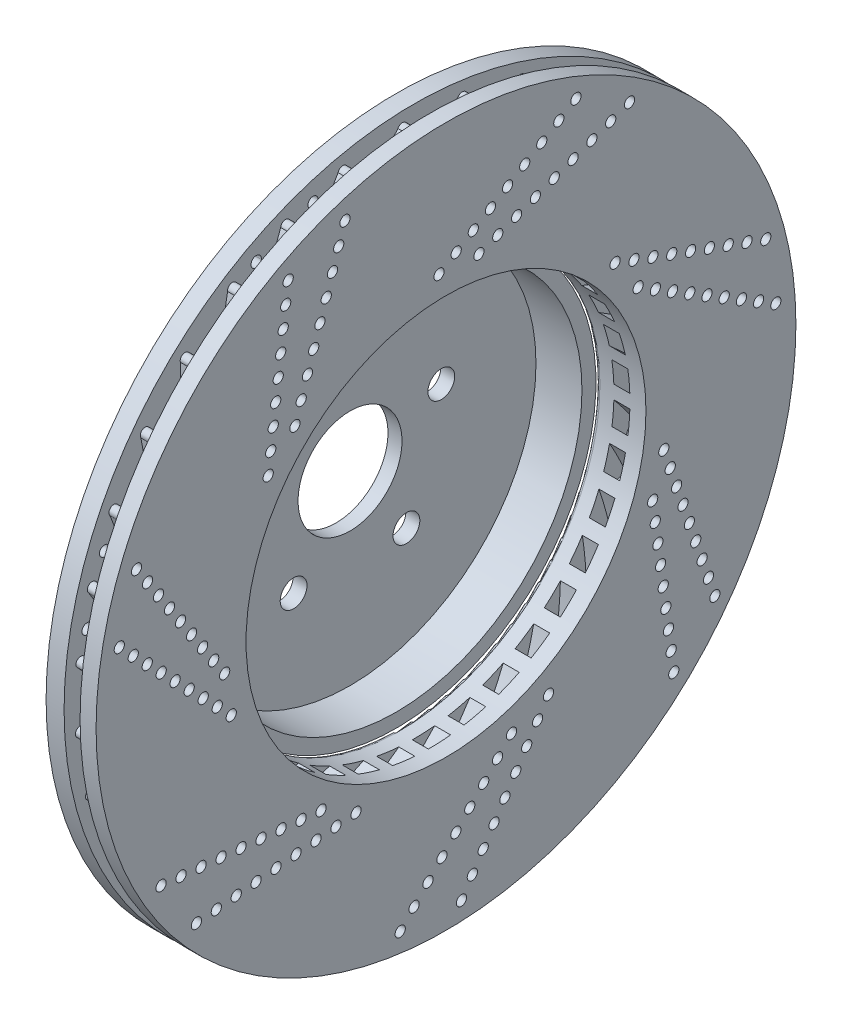
SolidWorks part; units mm, degrees
other "Markup1"
sketch "Sketch13"
ref_plane "Front Plane" through (0, 0, 0) normal (0, 0, 1) x (1, 0, 0)
ref_plane "Top Plane" through (0, 0, 0) normal (0, 1, 0) x (1, 0, 0)
ref_plane "Right Plane" through (0, 0, 0) normal (1, 0, 0) x (0, 0, -1)
sketch "Sketch2" plane through (0, 0, 0) normal (1, 0, 0) x (0, 0, -1)
  circle A0 centre (0, 0) radius 87.5
  dimension "D1" = 175
extrude "Boss-Extrude1" add sketch "Sketch2" along normal blind 4.5
sketch "Sketch3" plane through (4.5, 0, 0) normal (1, 0, 0) x (0, 0, -1)
  circle A0 centre (0, 0) radius 50
  dimension "D1" = 100
extrude "Cut-Extrude1" cut sketch "Sketch3" against normal through all
sketch "Sketch4" plane through (4.5, 0, 0) normal (1, 0, 0) x (0, 0, -1)
  line L0 (0, 0) -> (0, -87.5) construction
  line L1 (-22.5, -50.7346) -> (-71.6537, -55.6408) construction
  line L2 (-31.239, -45.8735) -> (-82.8176, -41.0887) construction
  circle A0 centre (0, 0) radius 55.5 construction
  circle A1 centre (0, 0) radius 87.5 construction
  circle A2 centre (-22.5, -50.7346) radius 1.28
  circle A3 centre (-31.239, -45.8735) radius 1.28
  circle A4 centre (-27.5, -51.2337) radius 1.28
  circle A5 centre (-32.5, -51.7327) radius 1.28
  circle A6 centre (-37.5, -52.2318) radius 1.28
  circle A7 centre (-42.5, -52.7309) radius 1.28
  circle A8 centre (-47.5, -53.2299) radius 1.28
  circle A9 centre (-52.5, -53.729) radius 1.28
  circle A10 centre (-57.5, -54.2281) radius 1.28
  circle A11 centre (-62.5, -54.7271) radius 1.28
  circle A12 centre (-36.239, -45.4097) radius 1.28
  circle A13 centre (-41.239, -44.9458) radius 1.28
  circle A14 centre (-46.239, -44.482) radius 1.28
  circle A15 centre (-51.2176, -44.0201) radius 1.28
  circle A16 centre (-46.239, -44.482) radius 1.28
  circle A17 centre (-56.2176, -43.5563) radius 1.28
  circle A18 centre (-61.2176, -43.0925) radius 1.28
  circle A19 centre (-66.2176, -42.6286) radius 1.28
  dimension "D1" = 111
  dimension "D2" = 2.56
  dimension "D3" = 10
  dimension "D7" = 5
  dimension "D15" = 5
  dimension "D16" = 5
  dimension "D17" = 5
  dimension "D18" = 5
  dimension "D19" = 5
  dimension "D20" = 5
  dimension "D21" = 5
  dimension "D4" = 22.5
  dimension "D5" = 84.3
  dimension "D6" = 95.3
  dimension "D8" = 5
  dimension "D9" = 5
  dimension "D10" = 5
  dimension "D11" = 5
  dimension "D12" = 5
  dimension "D13" = 5
  dimension "D14" = 5
  dimension "D22" = 5
extrude "Cut-Extrude6" cut sketch "Sketch4" against normal through all contours A12 | A3 | A13 | A14 | A15 | A17 | A19 | A18 | A11 | A10 | A9 | A8 | A7 | A6 | A5 | A4 | A2
pattern_circular "CirPattern1" count 7 over 360 about axis through (0, 0, 0) along (1, 0, 0) of "Cut-Extrude6"
ref_plane "Plane1" through (8.5, 0, 0) normal (1, 0, 0) x (0, 0, -1)
sketch "Sketch6" plane through (8.5, 0, 0) normal (1, 0, 0) x (0, 0, -1)
  circle A0 centre (0, 0) radius 50
  circle A1 centre (0, 0) radius 87.5
  dimension "D1" = 175
  dimension "D2" = 100
extrude "Boss-Extrude2" add sketch "Sketch6" along normal blind 4 separate body
sketch "Sketch7" plane through (12.5, 0, 0) normal (1, 0, 0) x (0, 0, -1)
  line L0 (0, 0) -> (0, -87.5) construction
  line L1 (-22.5, -50.7346) -> (-73.385, -55.8136) construction
  line L2 (-31.239, -45.8735) -> (-81.239, -41.2351) construction
  circle A0 centre (0, 0) radius 87.5 construction
  circle A1 centre (0, 0) radius 55.5 construction
  circle A2 centre (-22.5, -50.7346) radius 1.28
  circle A3 centre (-31.239, -45.8735) radius 1.28
  circle A4 centre (-27.5, -51.2337) radius 1.28
  circle A5 centre (-32.5, -51.7327) radius 1.28
  circle A6 centre (-37.5, -52.2318) radius 1.28
  circle A7 centre (-42.5, -52.7309) radius 1.28
  circle A8 centre (-47.4753, -53.2275) radius 1.28
  circle A9 centre (-52.4506, -53.7241) radius 1.28
  circle A10 centre (-57.4258, -54.2207) radius 1.28
  circle A11 centre (-62.4011, -54.7173) radius 1.28
  circle A12 centre (-71.239, -42.1628) radius 1.28
  circle A13 centre (-66.239, -42.6266) radius 1.28
  circle A14 centre (-61.239, -43.0905) radius 1.28
  circle A15 centre (-56.239, -43.5543) radius 1.28
  circle A16 centre (-51.239, -44.0181) radius 1.28
  circle A17 centre (-46.239, -44.482) radius 1.28
  circle A18 centre (-41.239, -44.9458) radius 1.28
  circle A19 centre (-36.239, -45.4097) radius 1.28
  dimension "D1" = 111
  dimension "D2" = 2.56
  dimension "D3" = 10
  dimension "D7" = 5
  dimension "D8" = 5
  dimension "D9" = 5
  dimension "D10" = 5
  dimension "D11" = 5
  dimension "D12" = 5
  dimension "D13" = 5
  dimension "D14" = 5
  dimension "D15" = 5
  dimension "D16" = 5
  dimension "D17" = 5
  dimension "D18" = 5
  dimension "D19" = 5
  dimension "D20" = 5
  dimension "D21" = 5
  dimension "D4" = 22.5
  dimension "D5" = 84.3
  dimension "D6" = 95.3
  dimension "5" = 5
extrude "Cut-Extrude8" cut sketch "Sketch7" against normal blind 13 contours A12 | A13 | A14 | A15 | A16 | A17 | A18 | A19 | A3 | A4 | A5 | A6 | A8 | A9 | A10 | A11 | A2 | A7
pattern_circular "CirPattern3" count 7 over 360 about axis through (0, 0, 0) along (1, 0, 0) of "Cut-Extrude8"
sketch "Sketch9" plane through (8.5, 0, 0) normal (-1, 0, 0) x (0, 0, 1)
  line L0 (0, 0) -> (0, -87.5) construction
  line L1 (0, 0) -> (-87.5, 0) construction
  line L2 (0, 0) -> (87.5, 0) construction
  circle A0 centre (0, 0) radius 87.5 construction
  circle A3 centre (0, 0) radius 87.5 construction
  arc A4 (68.4422, -47.3502) -> (68.033, -49.7205) centre (68.2376, -48.5353) cw
  arc A5 (17.9535, -46.6655) -> (21.0766, -45.3407) centre (0, 0) ccw
  arc A6 (9.3325, -49.1213) -> (12.642, -48.3754) centre (0, 0) ccw
  arc A7 (58.8876, -58.8101) -> (58.0617, -61.0692) centre (58.4746, -59.9396) cw
  arc A8 (0.4116, -49.9983) -> (3.8011, -49.8553) centre (0, 0) ccw
  arc A9 (47.4403, -68.3797) -> (46.2243, -70.4551) centre (46.8323, -69.4174) cw
  arc A10 (-8.5226, -49.2683) -> (-5.162, -49.7328) centre (0, 0) ccw
  arc A11 (34.4682, -75.7516) -> (32.9012, -77.5765) centre (33.6847, -76.6641) cw
  arc A12 (-17.1828, -46.9548) -> (-13.9592, -48.0119) centre (0, 0) ccw
  arc A13 (20.3883, -80.6888) -> (18.5206, -82.2046) centre (19.4545, -81.4467) cw
  arc A14 (-25.2908, -43.1321) -> (-22.3077, -44.7478) centre (0, 0) ccw
  arc A15 (5.6531, -83.0326) -> (3.5448, -84.1905) centre (4.599, -83.6116) cw
  arc A16 (-32.5859, -37.9231) -> (-29.9393, -40.0455) centre (0, 0) ccw
  arc A17 (-9.2638, -82.7076) -> (-11.5449, -83.4705) centre (-10.4043, -83.0891) cw
  arc A18 (-38.8337, -31.4952) -> (-36.6085, -34.0561) centre (0, 0) ccw
  arc A19 (-23.8829, -79.7244) -> (-26.2636, -80.0677) centre (-25.0733, -79.896) cw
  arc A20 (-43.8333, -24.055) -> (-42.1012, -26.9721) centre (0, 0) ccw
  arc A21 (-37.7344, -74.1787) -> (-40.1382, -74.0914) centre (-38.9363, -74.1351) cw
  arc A22 (-47.424, -15.8417) -> (-46.2406, -19.0212) centre (0, 0) ccw
  arc A23 (-50.3731, -66.2489) -> (-52.7227, -65.7337) centre (-51.5479, -65.9913) cw
  arc A24 (-49.4906, -7.1193) -> (-48.8939, -10.4589) centre (0, 0) ccw
  arc A25 (-61.3928, -56.1898) -> (-63.6126, -55.2634) centre (-62.5027, -55.7266) cw
  arc A26 (-49.9664, 1.832) -> (-49.9756, -1.5605) centre (0, 0) ccw
  arc A27 (-70.4393, -44.3247) -> (-72.458, -43.0168) centre (-71.4486, -43.6707) cw
  arc A28 (-48.8363, 10.7244) -> (-49.4512, 7.3881) centre (0, 0) ccw
  arc A29 (-77.2218, -31.0349) -> (-78.9745, -29.3876) centre (-78.0982, -30.2113) cw
  arc A30 (-46.1366, 19.2722) -> (-47.3373, 16.0992) centre (0, 0) ccw
  arc A31 (-81.5223, -16.7477) -> (-82.9527, -14.8139) centre (-82.2375, -15.7808) cw
  arc A32 (-41.954, 27.2004) -> (-43.7019, 24.2929) centre (0, 0) ccw
  arc A33 (-83.2026, -1.9222) -> (-84.2648, 0.2359) centre (-83.7337, -0.8431) cw
  arc A34 (-36.4229, 34.2545) -> (-38.6619, 31.7057) centre (0, 0) ccw
  arc A35 (-82.2087, 12.9651) -> (-82.8685, 15.2782) centre (-82.5386, 14.1216) cw
  arc A36 (-29.7212, 40.2076) -> (-32.3793, 38.0996) centre (0, 0) ccw
  arc A37 (-78.5726, 27.4357) -> (-78.8087, 29.8294) centre (-78.6907, 28.6325) cw
  arc A38 (-22.0642, 44.8684) -> (-25.0561, 43.2689) centre (0, 0) ccw
  arc A39 (-72.4111, 41.0244) -> (-72.216, 43.4219) centre (-72.3135, 42.2232) cw
  arc A40 (-13.6981, 48.087) -> (-16.9274, 47.0474) centre (0, 0) ccw
  arc A41 (-63.9222, 53.2947) -> (-63.3022, 55.6187) centre (-63.6122, 54.4567) cw
  arc A42 (-4.8917, 49.7601) -> (-8.2548, 49.3139) centre (0, 0) ccw
  arc A43 (-53.3788, 63.8519) -> (-52.3538, 66.028) centre (-52.8663, 64.94) cw
  arc A44 (4.0719, 49.8339) -> (0.6832, 49.9953) centre (0, 0) ccw
  arc A45 (-41.1198, 72.357) -> (-39.7227, 74.315) centre (-40.4212, 73.336) cw
  arc A46 (12.9047, 48.306) -> (9.5993, 49.0699) centre (0, 0) ccw
  arc A47 (-27.5391, 78.5364) -> (-25.8149, 80.2135) centre (-26.677, 79.3749) cw
  arc A48 (21.3227, 45.2255) -> (18.2068, 46.5673) centre (0, 0) ccw
  arc A49 (-13.0734, 82.1916) -> (-11.0773, 83.5338) centre (-12.0753, 82.8627) cw
  arc A50 (29.0553, 40.6914) -> (26.2291, 42.568) centre (0, 0) ccw
  arc A51 (1.8126, 83.2051) -> (4.0162, 84.1693) centre (2.9144, 83.6872) cw
  arc A52 (35.8541, 34.8494) -> (33.4084, 37.2005) centre (0, 0) ccw
  arc A53 (16.6403, 81.5443) -> (18.9807, 82.0996) centre (17.8105, 81.8219) cw
  arc A54 (41.5005, 27.8874) -> (39.5139, 30.6374) centre (0, 0) ccw
  arc A55 (30.9332, 77.2626) -> (33.3351, 77.3911) centre (32.1342, 77.3268) cw
  arc A56 (45.8131, 20.029) -> (44.3494, 23.0896) centre (0, 0) ccw
  arc A57 (44.2318, 70.4976) -> (46.6181, 70.1951) centre (45.425, 70.3464) cw
  arc A58 (48.6532, 11.5269) -> (47.7595, 14.7996) centre (0, 0) ccw
  arc A59 (56.1089, 61.4668) -> (58.4028, 60.7431) centre (57.2558, 61.1049) cw
  arc A60 (49.9295, 2.6543) -> (49.6346, 6.034) centre (0, 0) ccw
  arc A61 (66.1825, 50.4604) -> (68.3103, 49.3387) centre (67.2464, 49.8995) cw
  arc A62 (49.6011, -6.3036) -> (49.9143, -2.9256) centre (0, 0) ccw
  arc A63 (74.129, 37.8321) -> (76.0223, 36.3485) centre (75.0756, 37.0903) cw
  arc A64 (47.6784, -15.0589) -> (48.5898, -11.7911) centre (0, 0) ccw
  arc A65 (79.6929, 23.9879) -> (81.2909, 22.1901) centre (80.4919, 23.089) cw
  arc A66 (44.2233, -23.3302) -> (45.7036, -20.2777) centre (0, 0) ccw
  arc A67 (82.6954, 9.3727) -> (83.9467, 7.3184) centre (83.321, 8.3456) cw
  arc A68 (39.3468, -30.8517) -> (41.3484, -28.1125) centre (0, 0) ccw
  arc A69 (83.04, -5.5438) -> (83.9044, -7.7884) centre (83.4722, -6.6661) cw
  arc A70 (33.2058, -37.3815) -> (35.6642, -35.0437) centre (0, 0) ccw
  arc A71 (80.7156, -20.282) -> (81.1653, -22.645) centre (80.9405, -21.4635) cw
  arc A72 (25.9974, -42.7099) -> (28.8338, -40.8487) centre (0, 0) ccw
  arc A73 (75.797, -34.3684) -> (75.8176, -36.7737) centre (75.8073, -35.5711) cw
  spline S0 degree 2 poles (17.9535, -46.6655) (42.5032, -53.5102) (68.033, -49.7205) knots 0 0 0 1 1 1
  spline S1 degree 2 poles (21.0766, -45.3407) (44.3781, -52.1097) (68.4422, -47.3502) knots 0 0 0 1 1 1
  spline S2 degree 2 poles (9.3325, -49.1213) (32.2656, -60.2395) (58.0617, -61.0692) knots 0 0 0 1 1 1
  spline S3 degree 2 poles (12.642, -48.3754) (34.3604, -59.1963) (58.8876, -58.8101) knots 0 0 0 1 1 1
  spline S4 degree 2 poles (0.4116, -49.9983) (20.9909, -65.0327) (46.2243, -70.4551) knots 0 0 0 1 1 1
  spline S5 degree 2 poles (3.8011, -49.8553) (23.2383, -64.3803) (47.4403, -68.3797) knots 0 0 0 1 1 1
  spline S6 degree 2 poles (-8.5226, -49.2683) (9.0415, -67.7357) (32.9012, -77.5765) knots 0 0 0 1 1 1
  spline S7 degree 2 poles (-5.162, -49.7328) (11.3693, -67.495) (34.4682, -75.7516) knots 0 0 0 1 1 1
  spline S8 degree 2 poles (-17.1828, -46.9548) (-3.1985, -68.2615) (18.5206, -82.2046) knots 0 0 0 1 1 1
  spline S9 degree 2 poles (-13.9592, -48.0119) (-0.8651, -68.4404) (20.3883, -80.6888) knots 0 0 0 1 1 1
  spline S10 degree 2 poles (-25.2908, -43.1321) (-15.3356, -66.5934) (3.5448, -84.1905) knots 0 0 0 1 1 1
  spline S11 degree 2 poles (-22.3077, -44.7478) (-13.0717, -67.186) (5.6531, -83.0326) knots 0 0 0 1 1 1
  spline S12 degree 2 poles (-32.5859, -37.9231) (-26.9799, -62.785) (-11.5449, -83.4705) knots 0 0 0 1 1 1
  spline S13 degree 2 poles (-29.9393, -40.0455) (-24.8582, -63.7723) (-9.2638, -82.7076) knots 0 0 0 1 1 1
  spline S14 degree 2 poles (-38.8337, -31.4952) (-37.757, -56.9585) (-26.2636, -80.0677) knots 0 0 0 1 1 1
  spline S15 degree 2 poles (-36.6085, -34.0561) (-35.8457, -58.3088) (-23.8829, -79.7244) knots 0 0 0 1 1 1
  spline S16 degree 2 poles (-43.8333, -24.055) (-47.3206, -49.3014) (-40.1382, -74.0914) knots 0 0 0 1 1 1
  spline S17 degree 2 poles (-42.1012, -26.9721) (-45.6811, -50.9713) (-37.7344, -74.1787) knots 0 0 0 1 1 1
  spline S18 degree 2 poles (-47.424, -15.8417) (-55.3632, -40.0597) (-52.7227, -65.7337) knots 0 0 0 1 1 1
  spline S19 degree 2 poles (-46.2406, -19.0212) (-54.0482, -41.9955) (-50.3731, -66.2489) knots 0 0 0 1 1 1
  spline S20 degree 2 poles (-49.4906, -7.1193) (-61.6265, -29.5304) (-63.6126, -55.2634) knots 0 0 0 1 1 1
  spline S21 degree 2 poles (-48.8939, -10.4589) (-60.6783, -31.6699) (-61.3928, -56.1898) knots 0 0 0 1 1 1
  spline S22 degree 2 poles (-49.9664, 1.832) (-65.909, -18.0521) (-72.458, -43.0168) knots 0 0 0 1 1 1
  spline S23 degree 2 poles (-49.9756, -1.5605) (-65.358, -20.3265) (-70.4393, -44.3247) knots 0 0 0 1 1 1
  spline S24 degree 2 poles (-48.8363, 10.7244) (-68.0731, -5.9934) (-78.9745, -29.3876) knots 0 0 0 1 1 1
  spline S25 degree 2 poles (-49.4512, 7.3881) (-67.9371, -8.3297) (-77.2218, -31.0349) knots 0 0 0 1 1 1
  spline S26 degree 2 poles (-46.1366, 19.2722) (-68.0493, 6.2578) (-82.9527, -14.8139) knots 0 0 0 1 1 1
  spline S27 degree 2 poles (-47.3373, 16.0992) (-68.3327, 3.9348) (-81.5223, -16.7477) knots 0 0 0 1 1 1
  spline S28 degree 2 poles (-41.954, 27.2004) (-65.8383, 18.3079) (-84.2648, 0.2359) knots 0 0 0 1 1 1
  spline S29 degree 2 poles (-43.7019, 24.2929) (-66.5319, 16.0728) (-83.2026, -1.9222) knots 0 0 0 1 1 1
  spline S30 degree 2 poles (-36.4229, 34.2545) (-61.5113, 29.7696) (-82.8685, 15.2782) knots 0 0 0 1 1 1
  spline S31 degree 2 poles (-38.6619, 31.7057) (-62.5928, 27.6943) (-82.2087, 12.9651) knots 0 0 0 1 1 1
  spline S32 degree 2 poles (-29.7212, 40.2076) (-55.2072, 40.2744) (-78.8087, 29.8294) knots 0 0 0 1 1 1
  spline S33 degree 2 poles (-32.3793, 38.0996) (-56.6419, 38.4256) (-78.5726, 27.4357) knots 0 0 0 1 1 1
  spline S34 degree 2 poles (-22.0642, 44.8684) (-47.1287, 49.4848) (-72.216, 43.4219) knots 0 0 0 1 1 1
  spline S35 degree 2 poles (-25.0561, 43.2689) (-48.8705, 47.9219) (-72.4111, 41.0244) knots 0 0 0 1 1 1
  spline S36 degree 2 poles (-13.6981, 48.087) (-37.5355, 57.1048) (-63.3022, 55.6187) knots 0 0 0 1 1 1
  spline S37 degree 2 poles (-16.9274, 47.0474) (-39.5284, 55.8779) (-63.9222, 53.2947) knots 0 0 0 1 1 1
  spline S38 degree 2 poles (-4.8917, 49.7601) (-26.7359, 62.8893) (-52.3538, 66.028) knots 0 0 0 1 1 1
  spline S39 degree 2 poles (-8.2548, 49.3139) (-28.9157, 62.038) (-53.3788, 63.8519) knots 0 0 0 1 1 1
  spline S40 degree 2 poles (4.0719, 49.8339) (-15.0769, 66.6525) (-39.7227, 74.315) knots 0 0 0 1 1 1
  spline S41 degree 2 poles (0.6832, 49.9953) (-17.3737, 66.2041) (-41.1198, 72.357) knots 0 0 0 1 1 1
  spline S42 degree 2 poles (12.9047, 48.306) (-2.9333, 68.2734) (-25.8149, 80.2135) knots 0 0 0 1 1 1
  spline S43 degree 2 poles (9.5993, 49.0699) (-5.2733, 68.2424) (-27.5391, 78.5364) knots 0 0 0 1 1 1
  spline S44 degree 2 poles (21.3227, 45.2255) (9.3045, 67.7) (-11.0773, 83.5338) knots 0 0 0 1 1 1
  spline S45 degree 2 poles (18.2068, 46.5673) (6.9966, 68.0873) (-13.0734, 82.1916) knots 0 0 0 1 1 1
  spline S46 degree 2 poles (29.0553, 40.6914) (21.2433, 64.9507) (4.0162, 84.1693) knots 0 0 0 1 1 1
  spline S47 degree 2 poles (26.2291, 42.568) (19.0416, 65.7438) (1.8126, 83.2051) knots 0 0 0 1 1 1
  spline S48 degree 2 poles (35.8541, 34.8494) (32.4993, 60.1138) (18.9807, 82.0996) knots 0 0 0 1 1 1
  spline S49 degree 2 poles (33.4084, 37.2005) (30.4746, 61.2873) (16.6403, 81.5443) knots 0 0 0 1 1 1
  spline S50 degree 2 poles (41.5005, 27.8874) (42.7107, 53.3447) (33.3351, 77.3911) knots 0 0 0 1 1 1
  spline S51 degree 2 poles (39.5139, 30.6374) (40.9281, 54.8609) (30.9332, 77.2626) knots 0 0 0 1 1 1
  spline S52 degree 2 poles (45.8131, 20.029) (51.5494, 44.8612) (46.6181, 70.1951) knots 0 0 0 1 1 1
  spline S53 degree 2 poles (44.3494, 23.0896) (50.0662, 46.6713) (44.2318, 70.4976) knots 0 0 0 1 1 1
  spline S54 degree 2 poles (48.6532, 11.5269) (58.7313, 34.9357) (58.4028, 60.7431) knots 0 0 0 1 1 1
  spline S55 degree 2 poles (47.7595, 14.7996) (57.5951, 36.9816) (56.1089, 61.4668) knots 0 0 0 1 1 1
  spline S56 degree 2 poles (49.9295, 2.6543) (64.0255, 23.8874) (68.3103, 49.3387) knots 0 0 0 1 1 1
  spline S57 degree 2 poles (49.6346, 6.034) (63.2729, 26.1033) (66.1825, 50.4604) knots 0 0 0 1 1 1
  spline S58 degree 2 poles (49.6011, -6.3036) (67.2618, 12.0713) (76.0223, 36.3485) knots 0 0 0 1 1 1
  spline S59 degree 2 poles (49.9143, -2.9256) (66.917, 14.386) (74.129, 37.8321) knots 0 0 0 1 1 1
  spline S60 degree 2 poles (47.6784, -15.0589) (68.3363, -0.1327) (81.2909, 22.1901) knots 0 0 0 1 1 1
  spline S61 degree 2 poles (48.5898, -11.7911) (68.4103, 2.2063) (79.6929, 23.9879) knots 0 0 0 1 1 1
  spline S62 degree 2 poles (44.2233, -23.3302) (67.2144, -12.3325) (83.9467, 7.3184) knots 0 0 0 1 1 1
  spline S63 degree 2 poles (45.7036, -20.2777) (67.7049, -10.0443) (82.6954, 9.3727) knots 0 0 0 1 1 1
  spline S64 degree 2 poles (39.3468, -30.8517) (63.9322, -24.1359) (83.9044, -7.7884) knots 0 0 0 1 1 1
  spline S65 degree 2 poles (41.3484, -28.1125) (64.8233, -21.972) (83.04, -5.5438) knots 0 0 0 1 1 1
  spline S66 degree 2 poles (33.2058, -37.3815) (58.5951, -35.1636) (81.1653, -22.645) knots 0 0 0 1 1 1
  spline S67 degree 2 poles (35.6642, -35.0437) (59.8583, -33.1936) (80.7156, -20.282) knots 0 0 0 1 1 1
  spline S68 degree 2 poles (25.9974, -42.7099) (51.3748, -45.061) (75.8176, -36.7737) knots 0 0 0 1 1 1
  spline S69 degree 2 poles (28.8338, -40.8487) (52.9695, -43.3483) (75.797, -34.3684) knots 0 0 0 1 1 1
  dimension "D1" = 35
extrude "Boss-Extrude3" add sketch "Sketch9" along normal blind 7
sketch "Sketch11" plane through (0, 0, 0) normal (-1, 0, 0) x (0, 0, 1)
  circle A0 centre (0, 0) radius 50
  dimension "D1" = 100
extrude "Boss-Extrude4" add sketch "Sketch11" along normal blind 15 separate body
shell "Shell1" thickness 3.5
fillet "Fillet1" radius 1 1 edges at (0, 0, -50)
sketch "Sketch12" plane through (-15, 0, 0) normal (-1, 0, 0) x (0, 0, 1)
  circle A0 centre (0, 0) radius 24 construction
  circle A1 centre (0, 0) radius 13
  circle A2 centre (0, 24) radius 3.35
  circle A3 centre (0, 0) radius 24 construction
  circle A4 centre (22.8254, 7.4164) radius 3.35
  circle A5 centre (0, 0) radius 24 construction
  circle A6 centre (14.1068, -19.4164) radius 3.35
  circle A7 centre (0, 0) radius 24 construction
  circle A8 centre (-14.1068, -19.4164) radius 3.35
  circle A9 centre (0, 0) radius 24 construction
  circle A10 centre (-22.8254, 7.4164) radius 3.35
  point P20 (0, 0)
  dimension "D1" = 26
  dimension "D2" = 48
  dimension "D3" = 6.7
  dimension "D4" = 5
extrude "Cut-Extrude9" cut sketch "Sketch12" against normal blind 15
